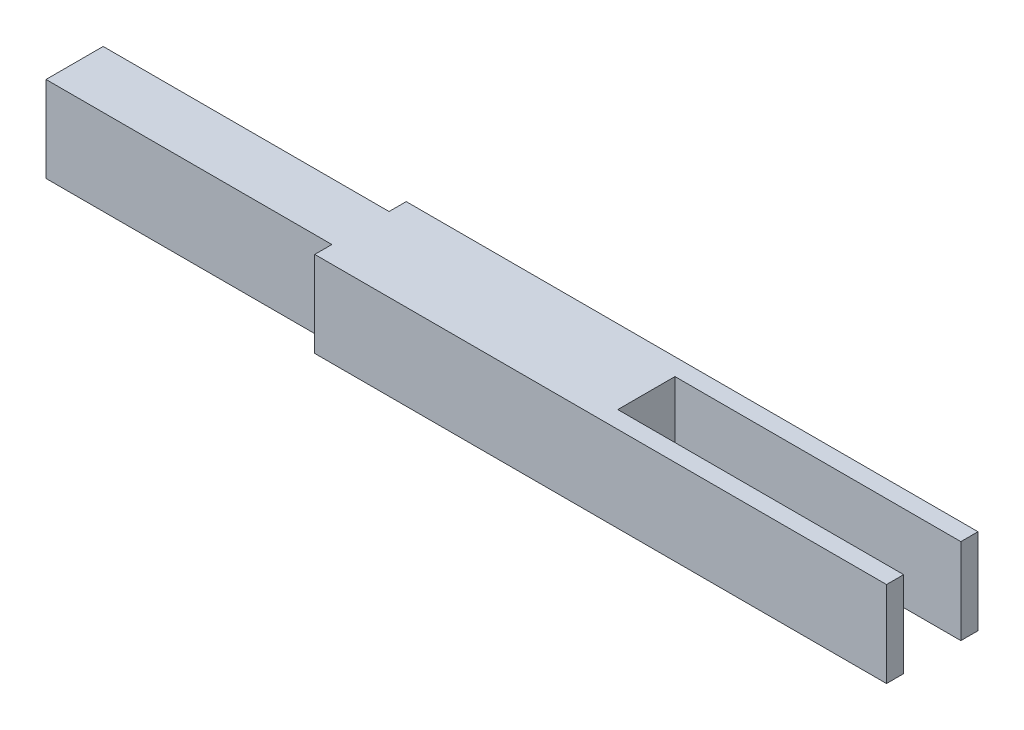
SolidWorks part; units mm, degrees
ref_plane "Front Plane" through (0, 0, 0) normal (0, 0, 1) x (1, 0, 0)
ref_plane "Top Plane" through (0, 0, 0) normal (0, 1, 0) x (1, 0, 0)
ref_plane "Right Plane" through (0, 0, 0) normal (1, 0, 0) x (0, 0, -1)
sketch "Sketch1" plane through (0, 0, 0) normal (0, 1, 0) x (1, 0, 0)
  line L0 (0, -5) -> (0, 5)
  line L1 (150, 8) -> (50, 8)
  line L2 (50, 8) -> (50, -5)
  line L3 (50, -5) -> (0, -5)
  line L4 (150, 8) -> (150, 5)
  line L5 (150, 5) -> (100, 5)
  line L6 (100, 5) -> (100, -5)
  line L7 (100, -5) -> (150, -5)
  line L8 (150, -5) -> (150, -8)
  line L9 (0, 0) -> (100, 0) construction
  line L12 (150, -8) -> (50, -8)
  line L13 (50, -8) -> (50, 5)
  line L14 (50, 5) -> (0, 5)
  point P2 (0, 0)
  dimension "D1" = 50
  dimension "D2" = 10
  dimension "D3" = 10
  dimension "D4" = 3
  dimension "D5" = 50
  dimension "D6" = 100
  dimension "D7" = 16
extrude "Boss-Extrude1" add sketch "Sketch1" along normal mid plane 15 contours L2 L9 L6 L5 L4 L1 | L9 L13 L12 L8 L7 L6 | L0 L9 L2 L14 | L9 L0 L3 L13 region at (25, 0, 2.5) region at (25, 0, -2.5) region at (88.6364, 0, 4.6818) region at (88.6364, 0, -4.6818)
